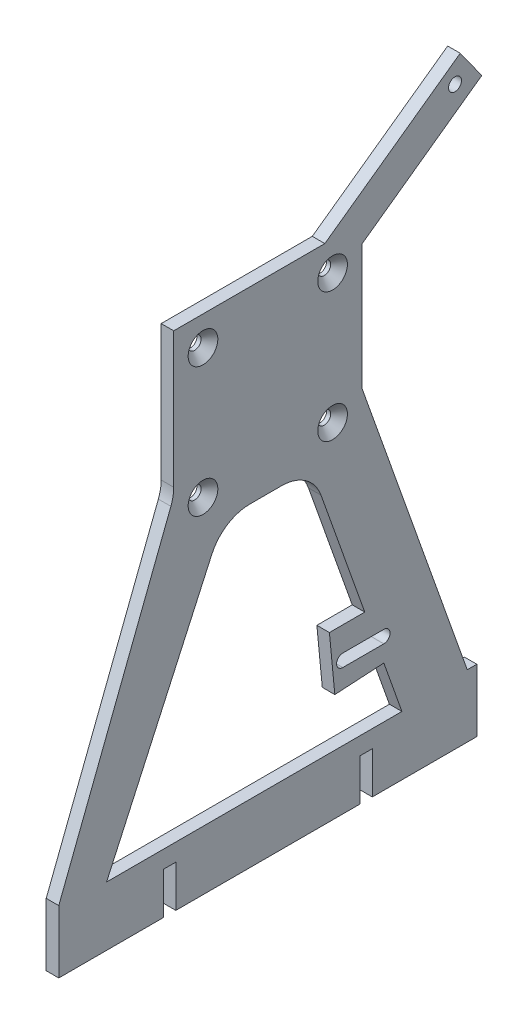
SolidWorks part; units mm, degrees
ref_plane "Front Plane" through (0, 0, 0) normal (0, 0, 1) x (1, 0, 0)
ref_plane "Top Plane" through (0, 0, 0) normal (0, 1, 0) x (1, 0, 0)
ref_plane "Right Plane" through (0, 0, 0) normal (1, 0, 0) x (0, 0, -1)
sketch "Sketch1" plane through (0, 0, 0) normal (1, 0, 0) x (0, 0, -1)
  line L21 (0, 15) -> (27.5, 86.0389)
  line L22 (27.5, 75.3197) -> (72.5, 75.3197)
  line L49 (50, 14.1691) -> (50, 0) construction
  line L50 (50, 14.1691) -> (50, 161.4393) construction
  line L51 (27.5, 75.3197) -> (27.5, 120.3197)
  line L52 (27.5, 120.3197) -> (72.5, 120.3197)
  line L53 (0, 0) -> (25, 0)
  line L54 (0, 0) -> (0, 15)
  line L56 (100, 0) -> (100, 15)
  line L65 (72.5, 75.3197) -> (72.5, 120.3197)
  line L66 (27.5, 75.3197) -> (72.5, 120.3197) construction
  line L67 (27.5, 120.3197) -> (72.5, 75.3197) construction
  line L75 (11.4392, 14.1691) -> (39.2826, 75.3197)
  line L76 (60.3659, 75.3197) -> (73.1989, 39.196)
  line L77 (72.5, 85.9722) -> (97.7129, 15)
  line L80 (97.7129, 15) -> (100, 15)
  line L88 (27.5, 86.0389) -> (39.2826, 75.3197)
  line L89 (60.3659, 75.3197) -> (72.5, 85.9722)
  line L92 (11.4392, 14.1691) -> (50, 14.1691)
  line L93 (50, 14.1691) -> (82.0897, 14.1691)
  line L94 (28, 0) -> (72, 0)
  line L96 (25, 0) -> (25, 10)
  line L97 (25, 10) -> (28, 10)
  line L98 (28, 0) -> (28, 10)
  line L100 (75, 0) -> (75, 10)
  line L101 (75, 10) -> (72, 10)
  line L102 (72, 0) -> (72, 10)
  line L103 (75, 0) -> (100, 0)
  line L104 (27.7379, 49.9649) -> (23.594, 40.8639)
  line L105 (73.1989, 39.196) -> (64.7416, 39.196)
  line L106 (64.7416, 39.196) -> (66.0363, 25.6881)
  line L107 (66.0363, 25.6881) -> (77.7539, 26.3742)
  line L108 (77.7539, 26.3742) -> (82.0897, 14.1691)
  line L109 (63.647, 120.3197) -> (96.0288, 143.5532)
  line L110 (96.0288, 143.5532) -> (101.1888, 136.3614)
  line L111 (101.1888, 136.3614) -> (71.3732, 114.969)
  line L112 (71.3732, 114.969) -> (63.647, 120.3197)
  line L113 (67.9564, 31.8454) -> (77.7539, 31.8454) construction
  line L114 (67.9564, 33.3454) -> (77.7539, 33.3454)
  line L115 (67.9564, 30.3454) -> (77.7539, 30.3454)
  circle A0 centre (94.7854, 137.7543) radius 1.55
  circle A6 centre (34.5, 82.3197) radius 1.55
  circle A7 centre (65.5, 82.3197) radius 1.55
  circle A8 centre (65.5, 113.3197) radius 1.55
  circle A9 centre (34.5, 113.3197) radius 1.55
  arc A11 (67.9564, 33.3454) -> (67.9564, 30.3454) centre (67.9564, 31.8454) ccw
  arc A12 (77.7539, 30.3454) -> (77.7539, 33.3454) centre (77.7539, 31.8454) ccw
  point P2 (50, 97.8197)
  point P43 (72.8551, 31.8454)
  point P55 (66.2101, 23.7097)
  point P56 (73.3878, 39.3158)
  point P57 (63.7414, 33.3454)
  point P58 (65.0138, 35.2376)
  point P59 (0, 0)
  point P60 (77.7539, 26.3742)
  point P61 (63.7041, 34.9661)
  point P62 (64.7416, 39.196)
  point P63 (66.0363, 25.6881)
  point P64 (0, 0)
  point P65 (0, 0)
  dimension "D2" = 3.1
  dimension "D3" = 3
  dimension "D4" = 2
  dimension "D5" = 2
  dimension "D6" = 3.1
  dimension "D10" = 3
  dimension "D8" = 10
  dimension "D7" = 15.5
  dimension "D9" = 15.5
  dimension "D11" = 10
  dimension "D12" = 3
  dimension "D13" = 25
  dimension "D14" = 25
  dimension "D15" = 45
  dimension "D16" = 45
  dimension "D17" = 100
  dimension "D18" = 15
  dimension "D20" = 15
extrude "Boss-Extrude2" add sketch "Sketch1" along normal blind 3 contours L51 L52 A0 | A6 | L52 L65 L22 L51 | L100 L101 L102 L94 L98 L97 L96 L53 L54 L21 L88 L75 L92 L93 L108 L107 L106 L105 L76 L89 L77 L80 L56 L103 | A9 | A8 | A7 | L115 A12 L114 A11 region at (0, 129.5231, -83.8901)
chamfer "Chamfer1" distance 2 angle 45 4 edges at (3, 82.3197, -36.05) (3, 82.3197, -67.05) (3, 113.3197, -67.05) (3, 113.3197, -36.05)
fillet "Fillet2" radius 10 3 edges at (1.5, 75.3197, -60.3659) (1.5, 75.3197, -39.2826) (1.5, 86.0389, -27.5)
